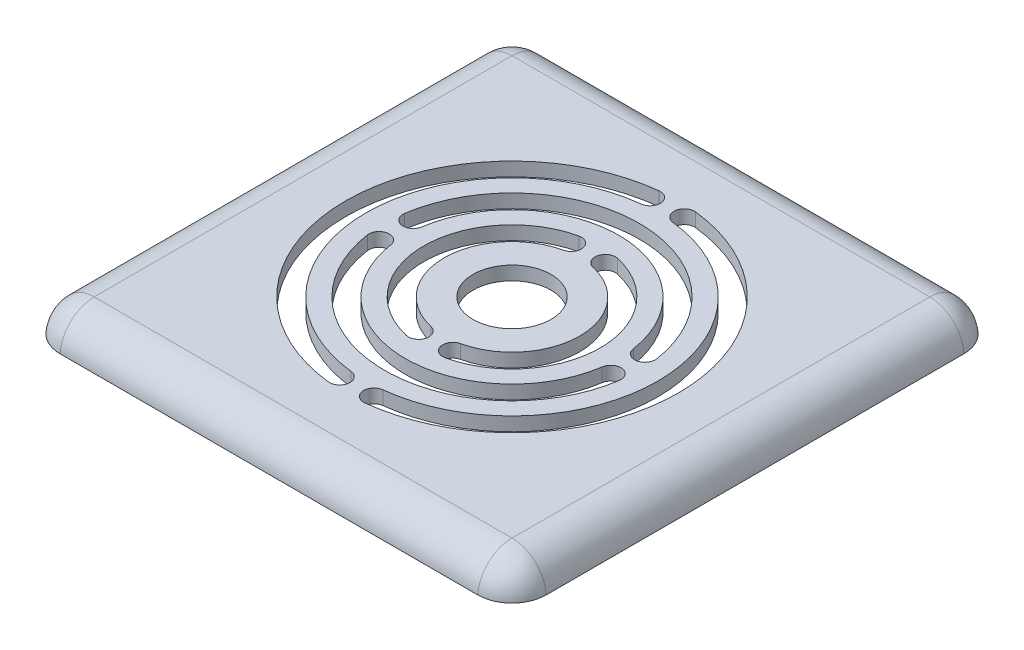
SolidWorks part; units mm, degrees
ref_plane "Спереди" through (0, 0, 0) normal (0, 0, 1) x (1, 0, 0)
ref_plane "Сверху" through (0, 0, 0) normal (0, 1, 0) x (1, 0, 0)
ref_plane "Справа" through (0, 0, 0) normal (1, 0, 0) x (0, 0, -1)
sketch "Эскиз1" plane through (0, 0, 0) normal (0, 1, 0) x (1, 0, 0)
  line L1 (-30.5, 35.5) -> (30.5, 35.5)
  line L2 (-35.5, 30.5) -> (-35.5, -30.5)
  line L3 (-30.5, -35.5) -> (30.5, -35.5)
  line L4 (35.5, 30.5) -> (35.5, -30.5)
  line L5 (-35.5, 35.5) -> (35.5, -35.5) construction
  line L6 (-35.5, -35.5) -> (35.5, 35.5) construction
  circle A0 centre (0, 0) radius 28.5 construction
  arc A1 (-30.5, -35.5) -> (-35.5, -30.5) centre (-30.5, -30.5) cw
  arc A2 (30.5, -35.5) -> (35.5, -30.5) centre (30.5, -30.5) ccw
  arc A3 (35.5, 30.5) -> (30.5, 35.5) centre (30.5, 30.5) ccw
  arc A4 (-30.5, 35.5) -> (-35.5, 30.5) centre (-30.5, 30.5) ccw
  dimension "D1" = 57
  dimension "D3" = 5
  dimension "D2" = 71
ref_plane "Плоскость1" through (0, 4.7, 0) normal (0, 1, 0) x (1, 0, 0)
extrude "Бобышка-Вытянуть1" add sketch "Эскиз1" along normal blind 4.7
fillet "Скругление1" radius 5 8 edges at (-34.0355, 4.7, 34.0355) (-35.5, 4.7, 0) (-34.0355, 4.7, -34.0355) (0, 4.7, -35.5) (34.0355, 4.7, -34.0355) (35.5, 4.7, 0) (34.0355, 4.7, 34.0355) (0, 4.7, 35.5)
sketch "Эскиз2" plane through (0, 0, 0) normal (0, 1, 0) x (1, 0, 0)
  circle A0 centre (0, 0) radius 29.5
  circle A1 centre (0, 0) radius 28.5 construction
  dimension "D1" = 1
extrude "Вырез-Вытянуть1" cut sketch "Эскиз2" along normal offset from surface (2.7 mm away) 2 up to face at (0, 4.7, 0)
sketch "Эскиз3" plane through (0, 4.7, 0) normal (0, 1, 0) x (1, 0, 0)
  line L0 (0, 22.8) -> (0, -22.8) construction
  line L1 (-22.8, 0) -> (22.8, 0) construction
  line L2 (-35.5, 35.5) -> (35.5, -35.5) construction
  line L3 (-35.5, -35.5) -> (35.5, 35.5) construction
  circle A0 centre (0, 0) radius 5.7
  circle A1 centre (0, 0) radius 11.4 construction
  circle A2 centre (0, 0) radius 17.1 construction
  circle A3 centre (0, 0) radius 22.8 construction
  arc A4 (2.5, 11.1225) -> (2.5, -11.1225) centre (0, 0) cw construction
  arc A5 (2.8289, -12.586) -> (2.8289, 12.586) centre (0, 0) ccw
  arc A6 (2.1711, -9.659) -> (2.1711, 9.659) centre (0, 0) ccw
  arc A7 (2.1711, -9.659) -> (2.8289, -12.586) centre (2.5, -11.1225) ccw
  arc A8 (2.8289, 12.586) -> (2.1711, 9.659) centre (2.5, 11.1225) ccw
  arc A9 (-2.5, 11.1225) -> (-2.5, -11.1225) centre (0, 0) ccw construction
  arc A10 (-2.8289, 12.586) -> (-2.8289, -12.586) centre (0, 0) ccw
  arc A11 (-2.1711, 9.659) -> (-2.1711, -9.659) centre (0, 0) ccw
  arc A12 (-2.1711, 9.659) -> (-2.8289, 12.586) centre (-2.5, 11.1225) ccw
  arc A13 (-2.8289, -12.586) -> (-2.1711, -9.659) centre (-2.5, -11.1225) ccw
  arc A14 (-16.9163, 2.5) -> (16.9163, 2.5) centre (0, 0) cw construction
  arc A15 (18.4001, 2.7193) -> (-18.4001, 2.7193) centre (0, 0) ccw
  arc A16 (15.4324, 2.2807) -> (-15.4324, 2.2807) centre (0, 0) ccw
  arc A17 (15.4324, 2.2807) -> (18.4001, 2.7193) centre (16.9163, 2.5) ccw
  arc A18 (-18.4001, 2.7193) -> (-15.4324, 2.2807) centre (-16.9163, 2.5) ccw
  arc A19 (-16.9163, -2.5) -> (16.9163, -2.5) centre (0, 0) ccw construction
  arc A20 (-18.4001, -2.7193) -> (18.4001, -2.7193) centre (0, 0) ccw
  arc A21 (-15.4324, -2.2807) -> (15.4324, -2.2807) centre (0, 0) ccw
  arc A22 (-15.4324, -2.2807) -> (-18.4001, -2.7193) centre (-16.9163, -2.5) ccw
  arc A23 (18.4001, -2.7193) -> (15.4324, -2.2807) centre (16.9163, -2.5) ccw
  arc A24 (-2.5, 22.6625) -> (-2.5, -22.6625) centre (0, 0) ccw construction
  arc A25 (-2.6645, 24.1535) -> (-2.6645, -24.1535) centre (0, 0) ccw
  arc A26 (-2.3355, 21.1716) -> (-2.3355, -21.1716) centre (0, 0) ccw
  arc A27 (-2.3355, 21.1716) -> (-2.6645, 24.1535) centre (-2.5, 22.6625) ccw
  arc A28 (-2.6645, -24.1535) -> (-2.3355, -21.1716) centre (-2.5, -22.6625) ccw
  arc A29 (2.5, -22.6625) -> (2.5, 22.6625) centre (0, 0) ccw construction
  arc A30 (2.6645, -24.1535) -> (2.6645, 24.1535) centre (0, 0) ccw
  arc A31 (2.3355, -21.1716) -> (2.3355, 21.1716) centre (0, 0) ccw
  arc A32 (2.3355, -21.1716) -> (2.6645, -24.1535) centre (2.5, -22.6625) ccw
  arc A33 (2.6645, 24.1535) -> (2.3355, 21.1716) centre (2.5, 22.6625) ccw
  point P12 (11.4, 0)
  point P22 (-11.4, 0)
  point P30 (0, 17.1)
  point P40 (0, -17.1)
  point P48 (-22.8, 0)
  point P56 (22.8, 0)
  dimension "D1" = 11.4
  dimension "D2" = 22.8
  dimension "D3" = 34.2
  dimension "D4" = 45.6
  dimension "D5" = 1.5
  dimension "D6" = 5
  dimension "D7" = 5
  dimension "D8" = 5
  dimension "D9" = 5
  dimension "D10" = 5
  dimension "D11" = 5
extrude "Вырез-Вытянуть2" cut sketch "Эскиз3" against normal through all
